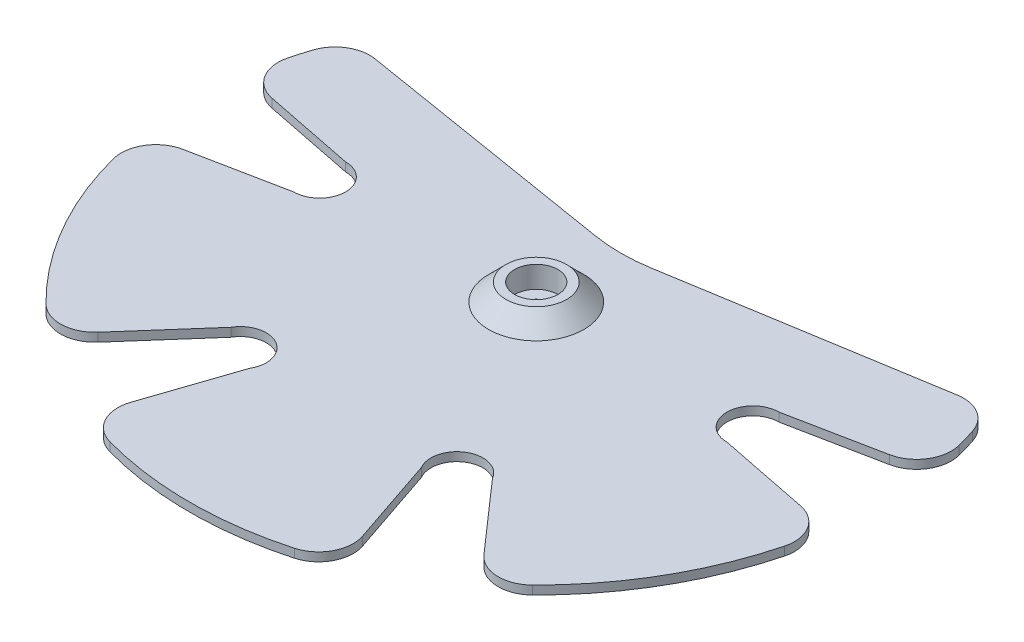
SolidWorks part; units mm, degrees
ref_plane "Plano frontal" through (0, 0, 0) normal (0, 0, 1) x (1, 0, 0)
ref_plane "Plano superior" through (0, 0, 0) normal (0, 1, 0) x (1, 0, 0)
ref_plane "Plano direito" through (0, 0, 0) normal (1, 0, 0) x (0, 0, -1)
sketch "Esboço1" plane through (0, 0, 0) normal (0, 1, 0) x (1, 0, 0)
  circle A0 centre (0, 0) radius 40
  dimension "D1" = 80
extrude "Ressalto-extrusão1" add sketch "Esboço1" along normal blind 1
sketch "Esboço2" plane through (0, 1, 0) normal (0, 1, 0) x (1, 0, 0)
  line L0 (0, 41.9322) -> (0, -42.8834) construction
  line L1 (43.2797, 0) -> (-44.548, 0) construction
  line L2 (25, 3) -> (40, 6)
  line L3 (25, -3) -> (40, -6)
  line L4 (15.0981, -20.1506) -> (25.1962, -31.641)
  line L5 (9.9019, -23.1506) -> (14.8038, -37.641)
  line L6 (-9.9019, -23.1506) -> (-14.8038, -37.641)
  line L7 (-15.0981, -20.1506) -> (-25.1962, -31.641)
  line L8 (-25, -3) -> (-40, -6)
  line L9 (-25, 3) -> (-40, 6)
  circle A0 centre (25, 0) radius 3
  circle A1 centre (0, 0) radius 40 construction
  circle A2 centre (40, 0) radius 6
  circle A3 centre (20, -34.641) radius 6
  circle A4 centre (12.5, -21.6506) radius 3
  circle A5 centre (-20, -34.641) radius 6
  circle A6 centre (-12.5, -21.6506) radius 3
  circle A7 centre (-40, 0) radius 6
  circle A8 centre (-25, 0) radius 3
  point P41 (0, 0)
  circle M2 centre (0, 0) radius 40
  dimension "D1" = 6
  dimension "D2" = 25
  dimension "D3" = 40
  dimension "D4" = 12
  dimension "D5" = 4
extrude "Corte-extrusão1" cut sketch "Esboço2" against normal blind 10 contours A6 L7 A5 L6 | L6 A5 L7 M2 | A6 | A4 L5 A3 L4 | A4 | L4 A3 L5 M2 | L8 A7 L9 M2 | A8 L9 A7 L8 | A8 | A2 L2 A0 L3 | L2 A2 L3 M2 | A0 M2 | A0 region at (31.3054, 1, 0) region at (25, 1, 0) region at (37.3658, 1, 0) region at (-37.3658, 1, 0) region at (-31.3054, 1, 0) region at (-25, 1, 0) region at (15.6527, 1, 27.1113) region at (18.6829, 1, 32.3598) region at (12.5, 1, 21.6506) region at (-18.6829, 1, 32.3598) region at (-15.6527, 1, 27.1113) region at (-12.5, 1, 21.6506)
sketch "Esboço3" plane through (0, 1, 0) normal (0, 1, 0) x (1, 0, 0)
  circle A0 centre (0, 0) radius 3.5
  dimension "D1" = 7
extrude "Ressalto-extrusão2" add sketch "Esboço3" along normal blind 2
sketch "Esboço4" plane through (0, 3, 0) normal (0, 1, 0) x (1, 0, 0)
  circle A0 centre (0, 0) radius 2.5
  dimension "D1" = 5
extrude "Corte-extrusão2" cut sketch "Esboço4" against normal blind 2.5 contours A0
chamfer "Chanfro1" distance 2 angle 45 1 edges at (0, 1, 3.5)
sketch "Esboço5" plane through (0, 1, 0) normal (0, 1, 0) x (1, 0, 0)
  line L0 (-36.8623, 15.5298) -> (0, 9.495)
  line L1 (0, 9.495) -> (36.8623, 15.5298)
  line L2 (36.8623, 15.5298) -> (36.8623, 44.4238)
  line L3 (36.8623, 44.4238) -> (-36.8623, 44.4238)
  line L4 (-36.8623, 44.4238) -> (-36.8623, 15.5298)
  arc A0 (39.5607, 5.9121) -> (-39.5607, 5.9121) centre (0, 0) ccw construction
extrude "Corte-extrusão3" cut sketch "Esboço5" against normal blind 3
fillet "Filete1" radius 4 1 edges at (36.8623, 0.5, -15.5298) type face fillet first side face at (18.4311, 0.5, -12.5124) second side face at (38.3622, 0.5, -10.7632)
sketch "Esboço6" plane through (0, 0.5, 0) normal (0, 1, 0) x (1, 0, 0)
  circle A0 centre (0, 0) radius 1.1
  dimension "D1" = 2.2
extrude "Corte-extrusão4" cut sketch "Esboço6" against normal blind 3
fillet "Filete2" radius 4 1 edges at (-36.8623, 0.5, -15.5298) type face fillet first side face at (-18.4311, 0.5, -12.5124) second side face at (-38.3622, 0.5, -10.7632)
fillet "Filete3" radius 4 1 edges at (-39.5607, 0.5, -5.9121) type face fillet first side face at (-38.8799, 0.5, -9.1107) second side face at (-32.2803, 0.5, -4.4561)
fillet "Filete4" radius 4 1 edges at (-39.5607, 0.5, 5.9121) type face fillet first side face at (-32.2803, 0.5, 4.4561) second side face at (-33.4358, 0.5, 19.3042)
fillet "Filete5" radius 4 1 edges at (-24.9004, 0.5, 31.3045) type face fillet first side face at (-32.6721, 0.5, 21.2406) second side face at (-19.9992, 0.5, 25.7276)
fillet "Filete6" radius 4 1 edges at (-14.6603, 0.5, 37.2166) type face fillet first side face at (-12.2811, 0.5, 30.1836) second side face at (0, 0.5, 38.6083)
fillet "Filete7" radius 4 1 edges at (14.6603, 0.5, 37.2166) type face fillet first side face at (12.2811, 0.5, 30.1836) second side face at (2.0588, 0.5, 38.9152)
fillet "Filete8" radius 4 1 edges at (24.9004, 0.5, 31.3045) type face fillet first side face at (19.9992, 0.5, 25.7276) second side face at (33.4358, 0.5, 19.3042)
fillet "Filete9" radius 4 1 edges at (39.5607, 0.5, 5.9121) type face fillet first side face at (32.2803, 0.5, 4.4561) second side face at (34.7309, 0.5, 17.6746)
fillet "Filete10" radius 4 1 edges at (39.5607, 0.5, -5.9121) type face fillet first side face at (32.2803, 0.5, -4.4561) second side face at (38.8799, 0.5, -9.1107)
fillet "Filete11" radius 20 1 edges at (0, 0.5, -9.495) type face fillet first side face at (-16.8078, 0.5, -12.2466) second side face at (16.8078, 0.5, -12.2466)
